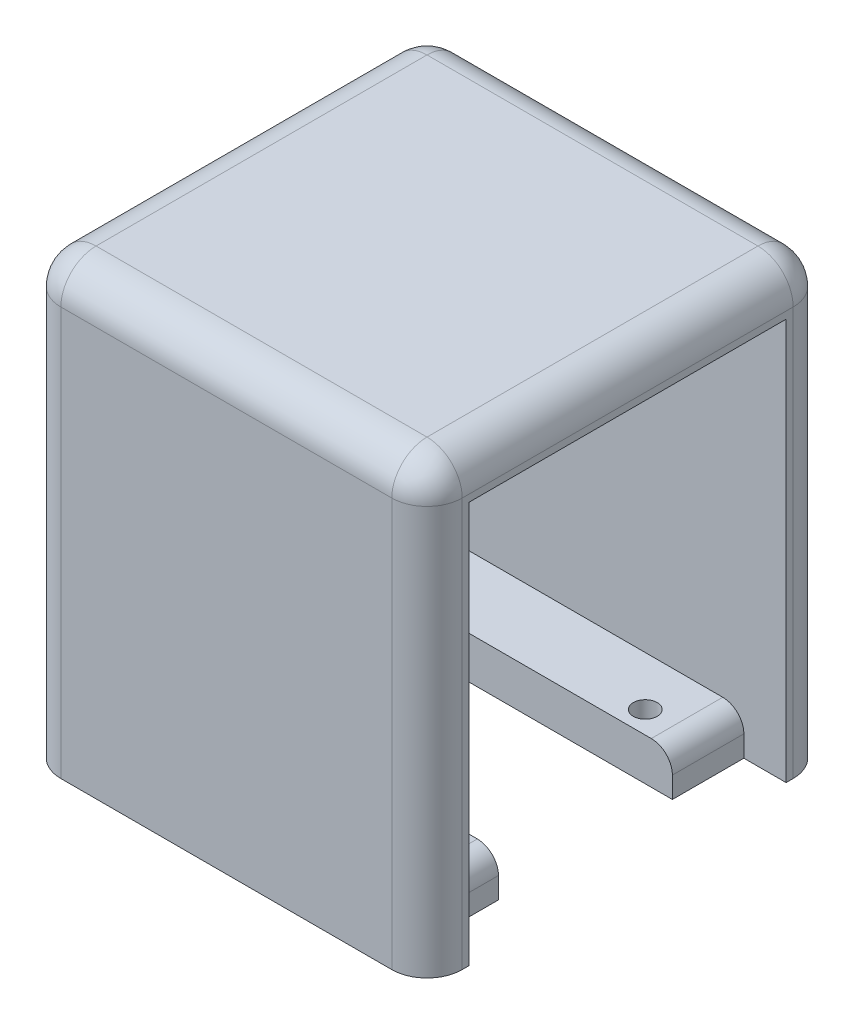
SolidWorks part; units mm, degrees
material "ABS"
ref_plane "Front Plane" through (0, 0, 0) normal (0, 0, 1) x (1, 0, 0)
ref_plane "Top Plane" through (0, 0, 0) normal (0, 1, 0) x (1, 0, 0)
ref_plane "Right Plane" through (0, 0, 0) normal (1, 0, 0) x (0, 0, -1)
sketch "Sketch1" plane through (0, 0, 0) normal (0, 1, 0) x (1, 0, 0)
  line L0 (-22.5, 22.5) -> (-22.5, -22.5)
  line L1 (-28.5, 28.5) -> (28.5, 28.5)
  line L2 (-28.5, 28.5) -> (-28.5, -28.5)
  line L3 (-28.5, -28.5) -> (28.5, -28.5)
  line L4 (28.5, 28.5) -> (28.5, -28.5)
  line L5 (-28.5, 28.5) -> (28.5, -28.5) construction
  line L6 (-28.5, -28.5) -> (28.5, 28.5) construction
  line L8 (22.5, -22.5) -> (22.5, -12.3505)
  line L10 (22.5, 12.3505) -> (-12.3505, 12.3505)
  line L11 (-12.3505, 12.3505) -> (-12.3505, -12.3505)
  line L14 (-12.3505, -12.3505) -> (22.5, -12.3505)
  line L15 (-22.5, 22.5) -> (22.5, 22.5)
  line L16 (28.5, 22.5) -> (28.5, 12.3505)
  line L18 (-22.5, -22.5) -> (22.5, -22.5)
  line L19 (28.5, -22.5) -> (28.5, -12.3505)
  line L20 (22.5, 12.3505) -> (22.5, 22.5)
  circle A0 centre (0, 0) radius 11 construction
  point P0 (0, 0)
  point P9 (15.5, 15.5)
  point P11 (15.5, -15.5)
  point P12 (-15.5, -15.5)
  point P16 (28.5, 28.5)
  point P29 (-15.5, 15.5)
  dimension "D3" = 22
  dimension "D5" = 31
sketch "Sketch3" plane through (0, 0, 0) normal (1, 0, 0) x (0, 0, -1)
  line L0 (-28.5, 0) -> (28.5, 0) construction
  line L1 (-28.5, 0) -> (28.5, 0) construction
  line L2 (-28.5, 0) -> (-28.5, 63) construction
  line L3 (-28.5, 63) -> (28.5, 63) construction
  line L4 (28.5, 0) -> (28.5, 63) construction
  line L5 (28.5, 0) -> (-28.5, 0) construction
  line L6 (28.5, 0) -> (-28.5, 0) construction
  line L8 (-22.5, 0) -> (-22.5, 57)
  line L9 (-22.5, 57) -> (22.5, 57)
  line L10 (22.5, 57) -> (22.5, 0)
  line L13 (-22.5, 57) -> (-28.5, 57) construction
  line L14 (22.5, 57) -> (28.5, 57) construction
  line L15 (28.5, 0) -> (-28.5, 0) construction
  line L16 (-22.5, 0) -> (22.5, 0)
  dimension "D1" = 57
  dimension "D2" = 6
  dimension "D4" = 45
  dimension "D5" = 57
extrude "Boss-Extrude3" add sketch "Sketch1" along normal up to vertex (63 mm away) contours L14 L11 L10 L0 | L4 L1 L2 L3 L14 L0 L10 L11 | L2 L1 L4 L3 region at (0, 0, -21.8636) region at (2.0954, 0, 0) up to point (0, 63, 28.5)
extrude "Cut-Extrude2" cut sketch "Sketch3" against normal up to vertex (22.5 mm away) and the other way through all up to point (-22.5, 0, 22.5)
extrude "Boss-Extrude4" add sketch "Sketch1<6>" along normal blind 6 contours L0 L18 L4 L14 L11 L10 L15 region at (0, 0, -21.8636)
sketch "Sketch1<6>" plane through (0, 0, 0) normal (0, 1, 0) x (1, 0, 0) same geometry as "Sketch1"
hole_wizard "Ø5.0mm Dowel Hole1" positions "Sketch6" profile "Sketch7" hole size "Ø5.0" standard "ANSI Metric"
sketch "Sketch6" plane through (0, 0, 0) normal (0, -1, 0) x (-1, 0, 0)
  point P0 (15.5, -15.5)
  point P3 (15.5, 15.5)
  point P6 (-15.5, 15.5)
  point P9 (-15.5, -15.5)
sketch "Sketch7" plane through (-15.5, 0, 15.5) normal (1, 0, 0) x (0, 0, -1)
  line L0 (0, 0) -> (0, 7.0215)
  line L1 (0, 7.0215) -> (1.7, 6)
  line L2 (1.7, 6) -> (1.7, 0)
  line L5 (1.7, 0) -> (0, 0)
  line L10 (0, 7.0215) -> (-1.7, 6) construction
  line L11 (0, -6.35) -> (0, 107.95) construction
  dimension "Hole Dia." = 3.4
  dimension "Hole Depth" = 6
  dimension "Drill Angle" = 118
fillet "Fillet1" radius 5 8 edges at (-28.5, 31.5, -28.5) (28.5, 31.5, -28.5) (-28.5, 31.5, 28.5) (28.5, 31.5, 28.5) (0, 63, -28.5) (0, 63, 28.5) (-28.5, 63, 0) (28.5, 63, 0)
fillet "Fillet2" radius 3 2 edges at (22.5, 6, 17.4252) (22.5, 6, -17.4252)
